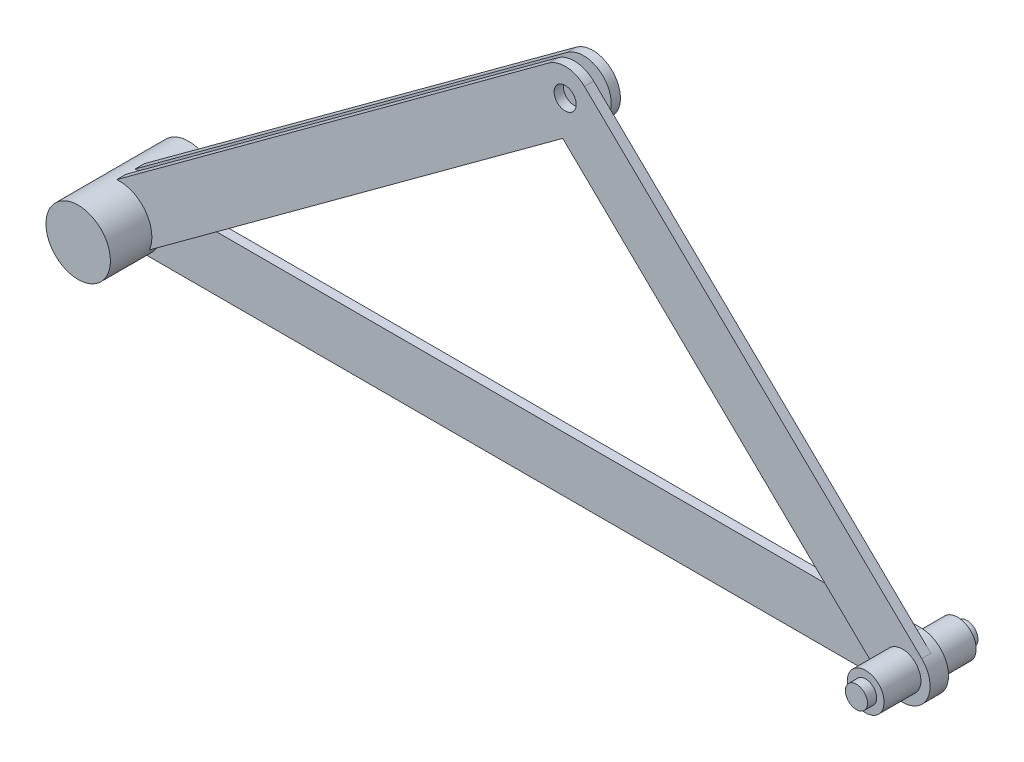
SolidWorks part; units mm, degrees
ref_plane "前视基准面" through (0, 0, 0) normal (0, 0, 1) x (1, 0, 0)
ref_plane "上视基准面" through (0, 0, 0) normal (0, 1, 0) x (1, 0, 0)
ref_plane "右视基准面" through (0, 0, 0) normal (1, 0, 0) x (0, 0, -1)
sketch "草图1" plane through (0, 0, 0) normal (0, 0, 1) x (1, 0, 0)
  line L1 (-225, 15) -> (225, 15)
  line L2 (-225, 15) -> (-225, -15)
  line L3 (-225, -15) -> (225, -15)
  line L4 (225, 15) -> (225, -15)
  line L5 (-225, 15) -> (225, -15) construction
  line L6 (-225, -15) -> (225, 15) construction
  point P0 (0, 0)
  dimension "D1" = 450
  dimension "D2" = 30
extrude "凸台-拉伸1" add sketch "草图1" along normal blind 5
fillet "圆角1" 2 edges at (-225, 15, 2.5) (-225, -15, 2.5) type full round first side face at (0, 15, 2.5) second side face at (0, -15, 2.5) middle face at (-225, 0, 2.5)
fillet "圆角2" 2 edges at (225, 15, 2.5) (225, -15, 2.5) type full round first side face at (7.5, 15, 2.5) second side face at (7.5, -15, 2.5) middle face at (225, 0, 2.5)
ref_plane "基准面1" through (0, 0, 2.5) normal (0, 0, 1) x (1, 0, 0)
sketch "草图2" plane through (0, 0, 5) normal (0, 0, 1) x (1, 0, 0)
  circle A0 centre (-215, 0) radius 6
  circle A1 centre (-215, 0) radius 10
  circle A2 centre (210, 0) radius 10
  circle A3 centre (210, 0) radius 6
  dimension "D1" = 12
  dimension "D2" = 12
extrude "凸台-拉伸2" add sketch "草图2" along normal mid plane 35
sketch "草图3" plane through (0, 0, 2.5) normal (0, 0, 1) x (1, 0, 0)
  line L0 (210, 0) -> (26.8824, 177.4625) construction
  line L1 (26.8824, 177.4625) -> (-215, 0) construction
  dimension "D1" = 255
  dimension "D2" = 300
sketch "草图4" plane through (0, 0, 5) normal (0, 0, 1) x (1, 0, 0)
  line L0 (210, 0) -> (26.8824, 177.4625) construction
  line L1 (199.561, -10.7716) -> (16.4434, 166.6908)
  line L2 (220.439, 10.7716) -> (37.3213, 188.2341)
  arc A0 (199.561, -10.7716) -> (220.439, 10.7716) centre (210, 0) ccw
  arc A1 (37.3213, 188.2341) -> (16.4434, 166.6908) centre (26.8824, 177.4625) ccw
  circle A2 centre (26.8824, 177.4625) radius 6
  point P4 (118.4412, 88.7312)
  dimension "D2" = 12
  dimension "D1" = 30
extrude "凸台-拉伸3" add sketch "草图4" along normal blind 5
sketch "草图5" plane through (0, 0, 5) normal (0, 0, 1) x (1, 0, 0)
  line L0 (-215, 0) -> (26.8824, 177.4625) construction
  line L1 (-223.8731, 12.0941) -> (18.0092, 189.5566)
  line L2 (-206.1269, -12.0941) -> (35.7555, 165.3683)
  arc A0 (-223.8731, 12.0941) -> (-206.1269, -12.0941) centre (-215, 0) ccw
  arc A1 (35.7555, 165.3683) -> (18.0092, 189.5566) centre (26.8824, 177.4625) ccw
  circle A2 centre (26.8824, 177.4625) radius 6
  point P4 (-94.0588, 88.7312)
  dimension "D1" = 15
extrude "凸台-拉伸4" add sketch "草图5" along normal blind 5
mirror "镜向1" about plane through (0, 0, 2.5) normal (0, 0, 1) of "凸台-拉伸4"
sketch "草图6" plane through (0, 0, 22.5) normal (0, 0, 1) x (1, 0, 0)
  circle A1 centre (210, 0) radius 10
  circle A2 centre (210, 0) radius 10
  dimension "D1" = 0
extrude "凸台-拉伸5" add sketch "草图6" along normal blind 7.5
sketch "草图7" plane through (0, 0, 30) normal (0, 0, 1) x (1, 0, 0)
  circle A0 centre (210, 0) radius 6
  dimension "D1" = 12
extrude "凸台-拉伸6" add sketch "草图7" along normal blind 5
mirror "镜向2" about plane through (0, 0, 5) normal (0, 0, 1) of "凸台-拉伸6", "凸台-拉伸5"
sketch "草图8" plane through (0, 0, 2.5) normal (0, 0, 1) x (1, 0, 0)
  circle A0 centre (-215, 0) radius 17.5
  dimension "D1" = 35
extrude "凸台-拉伸7" add sketch "草图8" against normal mid plane 60
ref_plane "基准面2" through (-232.5, 0, 0) normal (-1, 0, 0) x (0, 0, 1)
